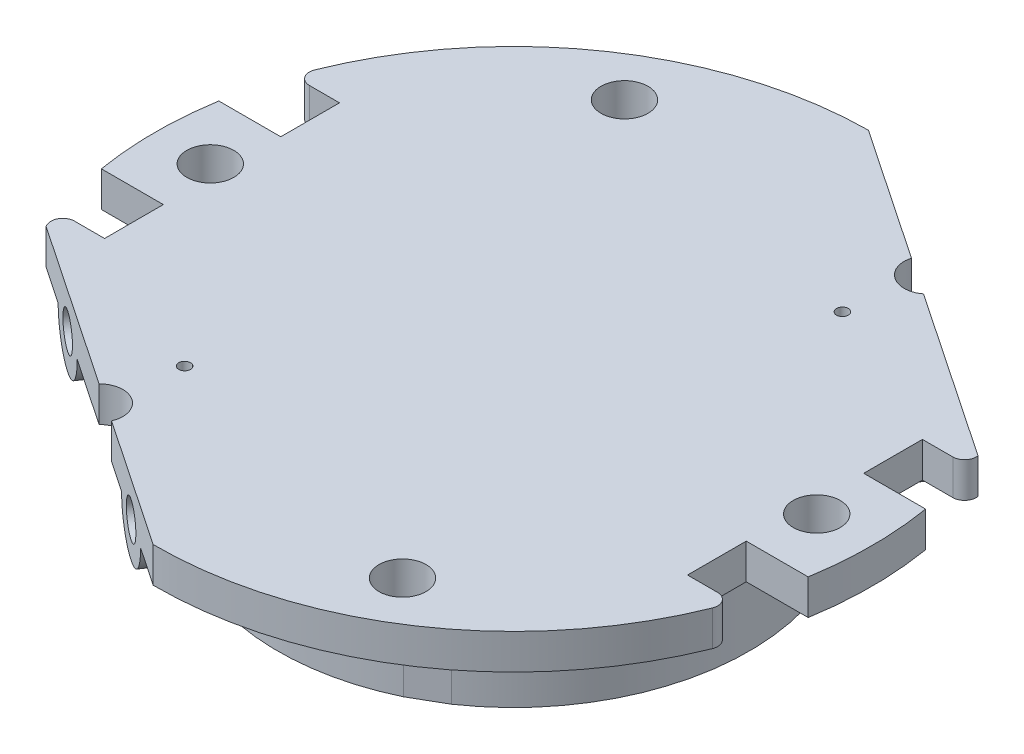
SolidWorks part; units mm, degrees
ref_plane "Alzado" through (0, 0, 0) normal (0, 0, 1) x (1, 0, 0)
ref_plane "Planta" through (0, 0, 0) normal (0, 1, 0) x (1, 0, 0)
ref_plane "Vista lateral" through (0, 0, 0) normal (1, 0, 0) x (0, 0, -1)
sketch "Croquis1" plane through (0, 0, 0) normal (0, 1, 0) x (1, 0, 0)
  circle A0 centre (0, 0) radius 30.5
extrude "Saliente-Extruir1" add sketch "Croquis1" along normal blind 3
sketch "Croquis5" plane through (0, 3, 0) normal (0, 1, 0) x (1, 0, 0)
  line L1 (28.8141, -5) -> (30.0874, -5)
  line L2 (28.8141, 5) -> (30.0874, 5)
  line L3 (-24.8141, 10) -> (-28.8141, 10)
  line L4 (24.8141, -5) -> (24.8141, -10)
  line L5 (-24.8141, -10) -> (-28.8141, -10)
  line L6 (24.8141, -5) -> (28.8141, -5)
  line L7 (24.8141, 5) -> (24.8141, 10)
  line L8 (-24.8141, 5) -> (-28.8141, 5)
  line L9 (-24.8141, 5) -> (-24.8141, 10)
  line L10 (-24.8141, -5) -> (-28.8141, -5)
  line L11 (-24.8141, -5) -> (-24.8141, -10)
  line L12 (24.8141, 5) -> (28.8141, 5)
  line L13 (24.8141, -10) -> (28.8141, -10)
  line L14 (24.8141, 10) -> (28.8141, 10)
  line L15 (-28.8141, 5) -> (-30.0874, 5)
  line L16 (-28.8141, -5) -> (-30.0874, -5)
  line L18 (-24.8141, 0) -> (-12.407, -21.4896)
  line L19 (-12.407, -21.4896) -> (12.407, -21.4896)
  line L20 (12.407, -21.4896) -> (24.8141, 0)
  line L21 (24.8141, 0) -> (12.407, 21.4896)
  line L22 (12.407, 21.4896) -> (-12.407, 21.4896)
  line L23 (-12.407, 21.4896) -> (-24.8141, 0)
  circle A0 centre (0, 0) radius 21.4896 construction
  circle A1 centre (0, 0) radius 30.5 construction
  arc A2 (-28.8141, 10) -> (-30.0874, 5) centre (0, 0) ccw
  arc A4 (-30.0874, -5) -> (-28.8141, -10) centre (0, 0) ccw
  arc A5 (30.0874, -5) -> (28.8141, -10) centre (0, 0) cw
  arc A6 (28.8141, 10) -> (30.0874, 5) centre (0, 0) cw
  circle M2 centre (0, 0) radius 30.5
extrude "Cortar-Extruir3" cut sketch "Croquis5" against normal blind 4 contours L10 L16 L5 L11 M2 | L15 L8 L9 L3 M2 | L14 L7 L12 L2 M2 | L4 L13 L1 L6 M2 region at (27.1844, 3, 7.3876) region at (-27.1844, 3, 7.3876) region at (27.1844, 3, -7.3876) region at (-27.1844, 3, -7.3876)
sketch "Croquis7" plane through (0, 3, 0) normal (0, 1, 0) x (1, 0, 0)
  line L2 (25.8141, 0) -> (12.907, 22.3556)
  line L3 (12.907, 22.3556) -> (-12.907, 22.3556)
  line L4 (-12.907, 22.3556) -> (-25.8141, 0)
  line L5 (-25.8141, 0) -> (-12.907, -22.3556)
  line L6 (-12.907, -22.3556) -> (12.907, -22.3556)
  line L7 (12.907, -22.3556) -> (25.8141, 0)
  circle A0 centre (25.8141, 0) radius 2
  circle A4 centre (-25.8141, 0) radius 2
  circle A5 centre (0, 0) radius 22.3556 construction
  circle A6 centre (12.907, 22.3556) radius 2
  circle A7 centre (-12.907, -22.3556) radius 2
  circle A8 centre (-12.907, 22.3556) radius 2
  circle A9 centre (12.907, -22.3556) radius 2
extrude "Cortar-Extruir4" cut sketch "Croquis7" against normal blind 10 contours A8 L4 L3 | A4 L4 L5 | A4 L5 L4 | A8 L3 L4 | L2 A6 L3 | L3 A6 L2 | L7 A0 L2 | L2 A0 L7 | A7 L5 L6 | A7 L6 L5 | L6 A9 L7 | L7 A9 L6 | A4 region at (24.7114, 3, 0) region at (26.3654, 3, 0) region at (12.3557, 3, -21.4007) region at (13.1827, 3, -22.8331) region at (13.1827, 3, 22.8331) region at (12.3557, 3, 21.4007) region at (-12.3557, 3, -21.4007) region at (-13.1827, 3, -22.8331) region at (-13.1827, 3, 22.8331) region at (-12.3557, 3, 21.4007) region at (-24.7114, 3, 0) region at (-26.3654, 3, 0)
sketch "Croquis8" plane through (0, 3, 0) normal (0, 1, 0) x (1, 0, 0)
  line L0 (0, 0) -> (12, 0)
  line L1 (12, 0) -> (12, 16)
  line L2 (0, 0) -> (-12, 0)
  line L3 (-12, 0) -> (-12, -16)
  circle A0 centre (12, 16) radius 0.5
  circle A1 centre (-12, -16) radius 0.5
extrude "Cortar-Extruir5" cut sketch "Croquis8" against normal blind 3 contours A1 | A0 region at (11.6564, 3, -16.3436) region at (-11.6564, 3, 15.6564)
sketch "Croquis9" plane through (0, 3, 0) normal (0, 1, 0) x (1, 0, 0)
  line L2 (-10, 17.3205) -> (-8.701, 18.0705)
  line L5 (25.6318, 16.5306) -> (27.1318, 13.9325)
  line L6 (-10, 17.3205) -> (-11.299, 16.5705)
  line L8 (10, -17.3205) -> (8.701, -18.0705)
  line L9 (10, -17.3205) -> (11.299, -16.5705)
  circle A0 centre (0, 0) radius 20.0562
  circle A1 centre (-12, -16) radius 3
  circle A2 centre (12, 16) radius 3
extrude "Saliente-Extruir2" add sketch "Croquis9" against normal blind 13 contours L2 L6 | L8 L9 region at (0, 3, 0)
sketch "Croquis11" plane through (14.0495, 0, -20.8293) normal (0.5592, 0, -0.829) x (-0.829, 0, -0.5592)
  line L1 (17.2916, 0) -> (-17.2916, 0)
  line L2 (17.2916, 0) -> (17.2916, 3)
  line L3 (17.2916, 3) -> (-17.2916, 3)
  line L4 (-17.2916, 0) -> (-17.2916, 3)
extrude "Saliente-Extruir3" add sketch "Croquis11" along normal blind 6
sketch "Croquis12" plane through (0, 3, 0) normal (0, 1, 0) x (1, 0, 0)
  circle A0 centre (12.907, 22.3556) radius 2
extrude "Cortar-Extruir7" cut sketch "Croquis12" against normal blind 3
sketch "Croquis13" plane through (17.4047, 0, -25.8035) normal (0.5592, 0, -0.829) x (-0.829, 0, -0.5592)
  line L0 (-17.2916, 0) -> (17.2916, 0)
  line L1 (17.2916, 3) -> (-17.2916, 3)
  line L2 (17.2916, 3) -> (-17.2916, 3) construction
  line L3 (17.2916, 0) -> (17.2916, 3) construction
  circle A1 centre (10, 0) radius 3
  circle A2 centre (-10, 0) radius 3
  circle A3 centre (10, 0) radius 1.5
  circle A5 centre (-10, 0) radius 1.5
  line M4 (-17.2916, 0) -> (17.2916, 0)
extrude "Saliente-Extruir4" add sketch "Croquis13" against normal blind 20 contours A3 L0 A1 | A3 L0 A1 | A5 L0 A2 | A5 L0 A2 | A5 M4 | A3 M4 region at (25.6951, 1.5671, -20.2116) region at (25.6951, -0.6366, -20.2116) region at (23.8297, -0.0671, -21.4698) region at (10.8337, 2.0739, -30.2358) region at (10.9797, -0.0671, -30.1373) region at (9.1143, -0.6366, -31.3955)
sketch "Croquis14" plane through (17.4047, 0, -25.8035) normal (0.5592, 0, -0.829) x (-0.829, 0, -0.5592)
  circle A0 centre (-10, 0) radius 1.5
  circle A1 centre (10, 0) radius 1.5
extrude "Cortar-Extruir8" cut sketch "Croquis14" against normal blind 6
sketch "Croquis15" plane through (0, 3, 0) normal (0, 1, 0) x (1, 0, 0)
  line L0 (28.3849, 11.16) -> (-0.2859, 30.4987)
  line L1 (28.3849, 11.16) -> (0.1409, -30.7136)
  line L2 (-0.2859, 30.4987) -> (-28.5299, -11.3749)
  line L3 (0.1409, -30.7136) -> (-28.5299, -11.3749)
  circle A0 centre (-0.2859, 0) radius 30.7165
  arc M12 (-28.8141, -10) -> (28.8141, -10) centre (0, 0) ccw
  circle M28 centre (-12.907, -22.3556) radius 2
extrude "Cortar-Extruir9" cut sketch "Croquis15" against normal blind 3 contours L3 M12 M28 region at (-15.494, 3, 22.7434)
sketch "Croquis16" plane through (-14.1945, 0, 21.0442) normal (-0.5592, 0, 0.829) x (0.829, 0, 0.5592)
  line L0 (-16.9088, 0) -> (-16.9088, 3)
  line L1 (-16.9088, 0) -> (16.78, 0)
  line L2 (-16.9088, 3) -> (16.78, 3)
  line L3 (16.78, 0) -> (16.78, 3)
extrude "Saliente-Extruir5" add sketch "Croquis16" along normal blind 6
sketch "Croquis17" plane through (0, 3, 0) normal (0, 1, 0) x (1, 0, 0)
  circle A0 centre (-12.907, -22.3556) radius 2
extrude "Cortar-Extruir10" cut sketch "Croquis17" against normal blind 3
sketch "Croquis18" plane through (-17.5497, 0, 26.0185) normal (-0.5592, 0, 0.829) x (0.829, 0, 0.5592)
  line L2 (-16.9088, 0) -> (16.78, 0) construction
  circle A0 centre (9.9356, 0) radius 3
  circle A1 centre (-10.0644, 0) radius 3
extrude "Saliente-Extruir6" add sketch "Croquis18" against normal blind 25
sketch "Croquis19" plane through (-17.5497, 0, 26.0185) normal (-0.5592, 0, 0.829) x (0.829, 0, 0.5592)
  circle A0 centre (-10.0644, 0) radius 1.5
  circle A1 centre (9.9356, 0) radius 1.5
extrude "Cortar-Extruir11" cut sketch "Croquis19" against normal blind 5
sketch "Croquis20" plane through (17.4047, 0, -25.8035) normal (0.5592, 0, -0.829) x (-0.829, 0, -0.5592)
  line L0 (17.2916, 3) -> (17.2916, 0)
  line L1 (17.2916, 0) -> (13, 0)
  line L2 (-7, 0) -> (7, 0) construction
  line L3 (7, 0) -> (-7, 0)
  line L4 (-13, 0) -> (-17.2916, 0)
  line L5 (-17.2916, 0) -> (-17.2916, 3)
  line L6 (-17.2916, 3) -> (17.2916, 3)
  arc A0 (13, 0) -> (7, 0) centre (10, 0) cw
  arc A1 (7, 0) -> (13, 0) centre (10, 0) ccw construction
  arc A2 (-7, 0) -> (-13, 0) centre (-10, 0) cw
extrude "Cortar-Extruir12" cut sketch "Croquis20" against normal blind 6
sketch "Croquis21" plane through (-17.5497, 0, 26.0185) normal (-0.5592, 0, 0.829) x (0.829, 0, 0.5592)
  line L0 (-13.0644, 0) -> (-16.9088, 0)
  line L1 (-16.9088, 0) -> (-16.9088, 3)
  line L2 (-16.9088, 3) -> (16.78, 3)
  line L3 (16.78, 3) -> (16.78, 0)
  line L4 (16.78, 0) -> (12.9356, 0)
  line L5 (6.9356, 0) -> (-7.0644, 0)
  arc A0 (-13.0644, 0) -> (-7.0644, 0) centre (-10.0644, 0) ccw
  arc A1 (6.9356, 0) -> (12.9356, 0) centre (9.9356, 0) ccw
extrude "Cortar-Extruir13" cut sketch "Croquis21" against normal blind 6
sketch "Croquis22" plane through (-14.1945, 0, 21.0442) normal (-0.5592, 0, 0.829) x (0.829, 0, 0.5592)
  circle A0 centre (-10.0644, 0) radius 1.5
  circle A1 centre (9.9356, 0) radius 1.5
extrude "Cortar-Extruir14" cut sketch "Croquis22" against normal blind 6
sketch "Croquis23" plane through (14.0495, 0, -20.8293) normal (0.5592, 0, -0.829) x (-0.829, 0, -0.5592)
  circle A0 centre (-10, 0) radius 1.5
  circle A1 centre (10, 0) radius 1.5
extrude "Cortar-Extruir15" cut sketch "Croquis23" against normal blind 6
fillet "Redondeo1" radius 1 4 edges at (-28.8141, 1.5, -10) (-28.8141, 1.5, 10) (28.8141, 1.5, 10) (28.8141, 1.5, -10)
sketch "Croquis24" plane through (0, 3, 0) normal (0, 1, 0) x (1, 0, 0)
  line L0 (0, 0) -> (-12.907, -22.3556)
  line L1 (-12.907, -22.3556) -> (-18.75, -32.476)
  circle A0 centre (0, 0) radius 37.5
  circle A1 centre (0, 0) radius 34.5
  circle A2 centre (-12.907, -22.3556) radius 2
  circle A3 centre (12.907, 22.3556) radius 2
